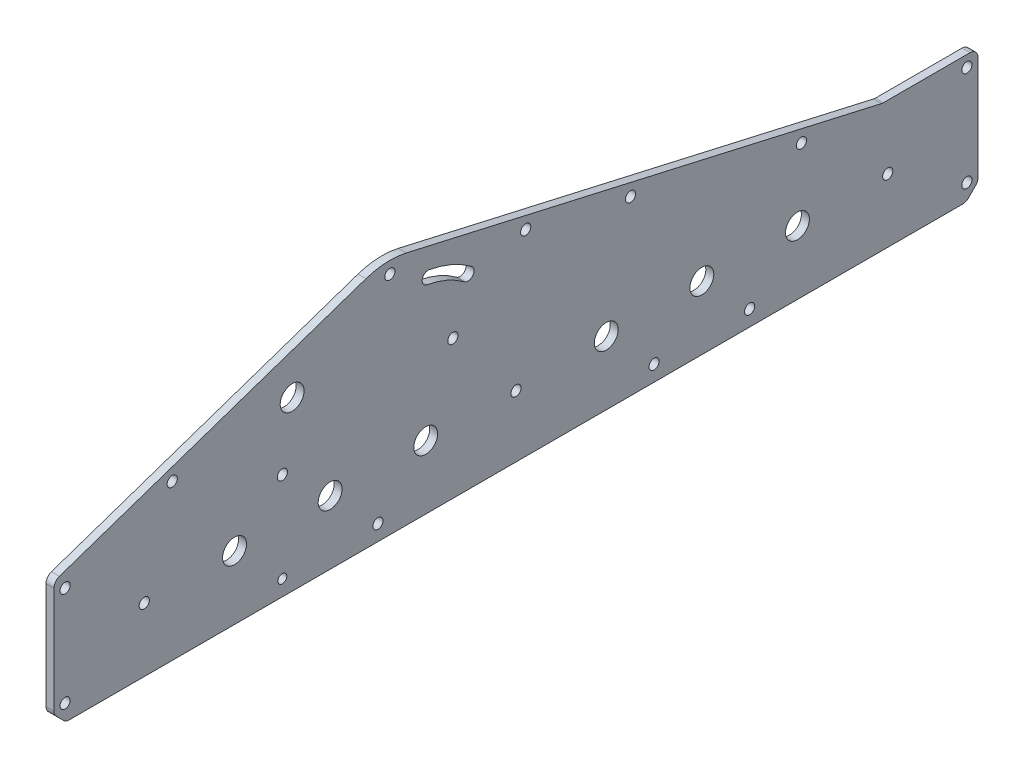
SolidWorks part; units mm, degrees
ref_plane "Front Plane" through (0, 0, 0) normal (0, 0, 1) x (1, 0, 0)
ref_plane "Top Plane" through (0, 0, 0) normal (0, 1, 0) x (1, 0, 0)
ref_plane "Right Plane" through (0, 0, 0) normal (1, 0, 0) x (0, 0, -1)
sketch "Sketch1" plane through (0, 0, 0) normal (1, 0, 0) x (0, 0, -1)
  line L0 (-184.15, 26.1937) -> (-59.8122, 68.5626)
  line L1 (-184.15, -24.6062) -> (184.15, -24.6062)
  line L2 (-184.15, -24.6062) -> (-184.15, 26.1937)
  line L3 (146.05, 26.1937) -> (184.15, 26.1937)
  line L4 (184.15, -24.6062) -> (184.15, 26.1937)
  line L9 (146.05, 26.1937) -> (-43.7083, 69.4049)
  arc A0 (-59.8122, 68.5626) -> (-43.7083, 69.4049) centre (-50.2741, 40.5715) cw
  arc A4 (-45.783, 38.8051) -> (-54.7652, 42.3379) centre (-50.2741, 40.5715) ccw construction
  arc A5 (-42.7051, 69.1579) -> (-57.8431, 69.1579) centre (-50.2741, 40.5715) ccw construction
  point P6 (0, -24.6062)
  dimension "D1" = 50.8
  dimension "D2" = 368.3
  dimension "D3" = 24.6062
  dimension "D5" = 38.1
extrude "Boss-Extrude1" add sketch "Sketch1" along normal blind 3.175
chamfer "Chamfer1" distance 4.7625 angle 45 2 edges at (1.5875, -24.6062, -184.15) (1.5875, -24.6062, 184.15)
fillet "Fillet1" radius 3.175 7 edges at (1.5875, -24.6062, -179.3875) (1.5875, -19.8437, -184.15) (1.5875, 26.1937, -184.15) (1.5875, -24.6062, 179.3875) (1.5875, -19.8437, 184.15) (1.5875, 26.1937, 184.15) (1.5875, 26.1937, -146.05)
sketch "Sketch4" plane through (3.175, 0, 0) normal (1, 0, 0) x (0, 0, -1)
  circle A0 centre (-137.0088, 37.226) radius 1.905 construction
  circle A2 centre (3.8736, 53.6853) radius 1.905 construction
  circle A3 centre (45.6663, 44.1684) radius 1.905 construction
  circle A4 centre (113.7728, 28.6594) radius 1.905 construction
  circle A5 centre (-25.1593, 30.6938) radius 2.032 construction
  circle A6 centre (-50.2741, 65.3805) radius 1.905 construction
  circle A7 centre (148.1579, 0.7938) radius 2.032 construction
  circle A8 centre (179.705, 21.7488) radius 1.905 construction
  circle A9 centre (179.705, -18.0026) radius 1.905 construction
  circle A11 centre (93.1246, -18.3223) radius 1.905 construction
  point P3 (0, 0)
  point P9 (55.0246, -18.3223)
  point P11 (-55.0246, -18.3223)
  point P13 (-179.705, 21.7487)
  point P15 (-179.705, -18.0026)
  point P17 (179.705, 21.7488)
  point P19 (148.1579, 0.7938)
  point P21 (-148.1579, 0.7937)
  point P25 (-93.1246, 17.5943)
  point P28 (-137.0088, 37.226)
  point P32 (3.8736, 53.6853)
  point P34 (45.6663, 44.1684)
  point P36 (113.7728, 28.6594)
  point P54 (-25.1593, 30.6938)
  point P59 (-50.2741, 65.3805)
  point P71 (179.705, -18.0026)
  point P76 (93.1246, -18.3223)
hole_wizard "#8 Clearance Hole1" positions "Sketch4" profile "Sketch5" hole size "#8" standard "ANSI Inch" end condition up to next
sketch "Sketch5" plane through (3.175, 0, 0) normal (0, 1, 0) x (0, 0, -1)
  line L0 (0, 0) -> (0, 3.175)
  line L1 (0, 3.175) -> (2.032, 3.175)
  line L2 (2.032, 3.175) -> (2.032, 0)
  line L5 (2.032, 0) -> (0, 0)
  line L11 (0, -6.35) -> (0, 107.95) construction
  dimension "Thru Hole Dia." = 4.064
  dimension "Thru Hole Depth" = 3.175
sketch "Sketch6" plane through (3.175, 0, 0) normal (1, 0, 0) x (0, 0, -1)
  point P0 (-93.1246, -18.3223)
hole_wizard "#8 Clearance Hole2" positions "Sketch6" profile "Sketch7" hole size "#8" standard "ANSI Inch" end condition up to next
sketch "Sketch7" plane through (3.175, -18.3223, 93.1246) normal (0, 1, 0) x (0, 0, -1)
  line L0 (0, 0) -> (0, 3.175)
  line L1 (0, 3.175) -> (1.778, 3.175)
  line L2 (1.778, 3.175) -> (1.778, 0)
  line L5 (1.778, 0) -> (0, 0)
  line L11 (0, -6.35) -> (0, 107.95) construction
  dimension "Thru Hole Dia." = 3.556
  dimension "Thru Hole Depth" = 3.175
sketch "Sketch8" plane through (3.175, 0, 0) normal (1, 0, 0) x (0, 0, -1)
  circle A0 centre (-89.211, 42.2593) radius 4.7625 construction
  circle A1 centre (35.9746, 0.7937) radius 7.239 construction
  circle A2 centre (-74.0746, 0.7938) radius 7.239 construction
  circle A3 centre (-112.1746, 0.7937) radius 4.7625 construction
  point P0 (-112.1746, 0.7937)
  point P1 (-74.0746, 0.7938)
  point P3 (-35.9746, 0.7938)
  point P5 (35.9746, 0.7937)
  point P7 (74.0746, 0.7937)
  point P9 (112.1746, 0.7937)
  point P13 (-89.211, 42.2593)
  point P18 (0, 0)
  point P21 (0, 0)
  point P24 (0, 0)
hole_wizard "3/8 Clearance Hole1" positions "Sketch8" profile "Sketch9" hole size "3/8" standard "ANSI Inch" end condition up to next
sketch "Sketch9" plane through (3.175, 0.7937, 112.1746) normal (0, 1, 0) x (0, 0, -1)
  line L0 (0, 0) -> (0, 3.175)
  line L1 (0, 3.175) -> (4.7625, 3.175)
  line L2 (4.7625, 3.175) -> (4.7625, 0)
  line L5 (4.7625, 0) -> (0, 0)
  line L11 (0, -6.35) -> (0, 107.95) construction
  dimension "Thru Hole Dia." = 9.525
  dimension "Thru Hole Depth" = 3.175
sketch "Sketch10" plane through (3.175, 0, 0) normal (1, 0, 0) x (0, 0, -1)
  arc A0 (-34.5594, 59.0407) -> (-35.4169, 54.2915) centre (-34.9881, 56.6661) ccw construction
  arc A1 (-20.5473, 47.8719) -> (-35.4169, 54.2915) centre (-41.7582, 19.1724) ccw construction
  arc A2 (-20.5473, 47.8719) -> (-17.6789, 51.753) centre (-19.1131, 49.8125) ccw construction
  arc A3 (-17.6789, 51.753) -> (-34.5594, 59.0407) centre (-41.7582, 19.1724) ccw construction
  arc A4 (-34.5594, 59.0407) -> (-35.4169, 54.2915) centre (-34.9881, 56.6661) ccw
  arc A5 (-20.5473, 47.8719) -> (-35.4169, 54.2915) centre (-41.7582, 19.1724) ccw
  arc A6 (-20.5473, 47.8719) -> (-17.6789, 51.753) centre (-19.1131, 49.8125) ccw
  arc A7 (-17.6789, 51.753) -> (-34.5594, 59.0407) centre (-41.7582, 19.1724) ccw
extrude "Cut-Extrude1" cut sketch "Sketch10" against normal through all
